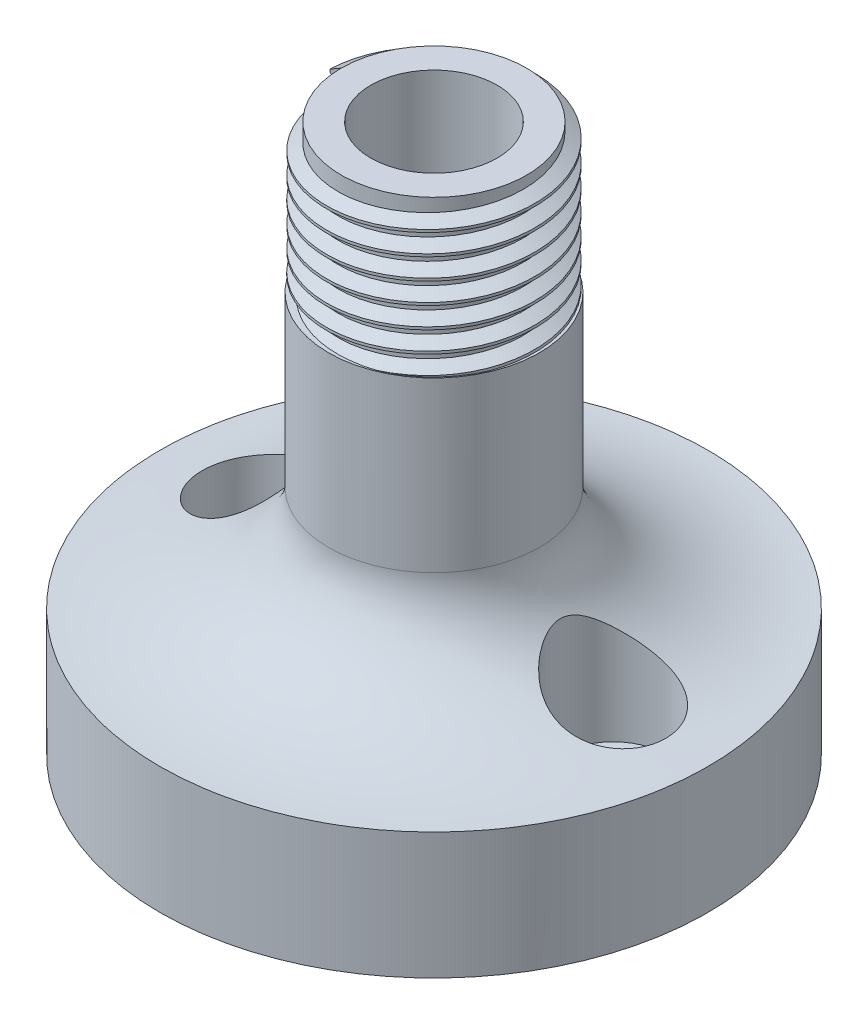
SolidWorks part; units mm, degrees
material "ABS"
ref_plane "Front Plane" through (0, 0, 0) normal (0, 0, 1) x (1, 0, 0)
ref_plane "Top Plane" through (0, 0, 0) normal (0, 1, 0) x (1, 0, 0)
ref_plane "Right Plane" through (0, 0, 0) normal (1, 0, 0) x (0, 0, -1)
sketch "Sketch1" plane through (0, 0, 0) normal (0, 1, 0) x (1, 0, 0)
  circle A0 centre (0, 0) radius 13
  circle A1 centre (-8.5, 0) radius 1.1
  circle A2 centre (8.5, 0) radius 1.1
  circle A3 centre (0, 0) radius 3
  dimension "D1" = 26
  dimension "D2" = 2.2
  dimension "D4" = 8.5
  dimension "D5" = 6
  dimension "D3" = 8.5
extrude "Boss-Extrude1" add sketch "Sketch1" along normal blind 3
sketch "Sketch2" plane through (0, 3, 0) normal (0, 1, 0) x (1, 0, 0)
  circle A0 centre (-8.5, 0) radius 2.5
  circle A1 centre (8.5, 0) radius 2.5
  circle A2 centre (0, 0) radius 13
  circle A3 centre (0, 0) radius 13 construction
  circle A4 centre (-8.5, 0) radius 1.1 construction
  circle A5 centre (8.5, 0) radius 1.1 construction
  circle A6 centre (0, 0) radius 3
  circle A7 centre (0, 0) radius 3 construction
  dimension "D1" = 5
extrude "Boss-Extrude2" add sketch "Sketch2" along normal blind 3
sketch "Sketch3" plane through (0, 6, 0) normal (0, 1, 0) x (1, 0, 0)
  circle A0 centre (0, 0) radius 5
  circle A1 centre (0, 0) radius 3
  circle A2 centre (0, 0) radius 3 construction
  dimension "D1" = 10
extrude "Boss-Extrude3" add sketch "Sketch3" along normal blind 20
fillet "Fillet1" radius 8 1 edges at (0, 6, 5) second distance 5 first distance on face at (-8.5, 6, 2.5)
sketch "Sketch10" plane through (0, 26, 0) normal (0, 1, 0) x (1, 0, 0)
  circle A1 centre (0, 0) radius 5
  circle A2 centre (0, 0) radius 5 construction
  circle A3 centre (0, 0) radius 4.4
  dimension "D1" = 0.6
extrude "Cut-Extrude1" cut sketch "Sketch10" against normal blind 7
thread "Thread1" pitch 1 method extrude profile "Thread Profile1" start angle 0, offset 0, length 7, pitch 1, diameter 8.8
ref_plane "Plane1" through (-4.4, 26, 0) normal (0, 0, 1) x (-1, 0, 0)
sketch "Thread Profile1" plane through (-4.4, 26, 0) normal (0, 0, 1) x (-1, 0, 0)
  line L0 (0, 0) -> (0, 1) construction
  line L1 (0, 0) -> (0.5413, 0.3125)
  line L2 (0.5413, 0.3125) -> (0.5413, 0.4375)
  line L3 (0.5413, 0.4375) -> (0, 0.75)
  line L4 (0.5413, 0.375) -> (0, 0.375) construction
  line L11 (0, 0) -> (0, 0.75)
  point P2 (0, 0)
  dimension "Pitch" = 1
  dimension "Profile_Angle" = 60
  dimension "Profile_Land" = 0.125
  dimension "Profile_Height" = 0.5413
